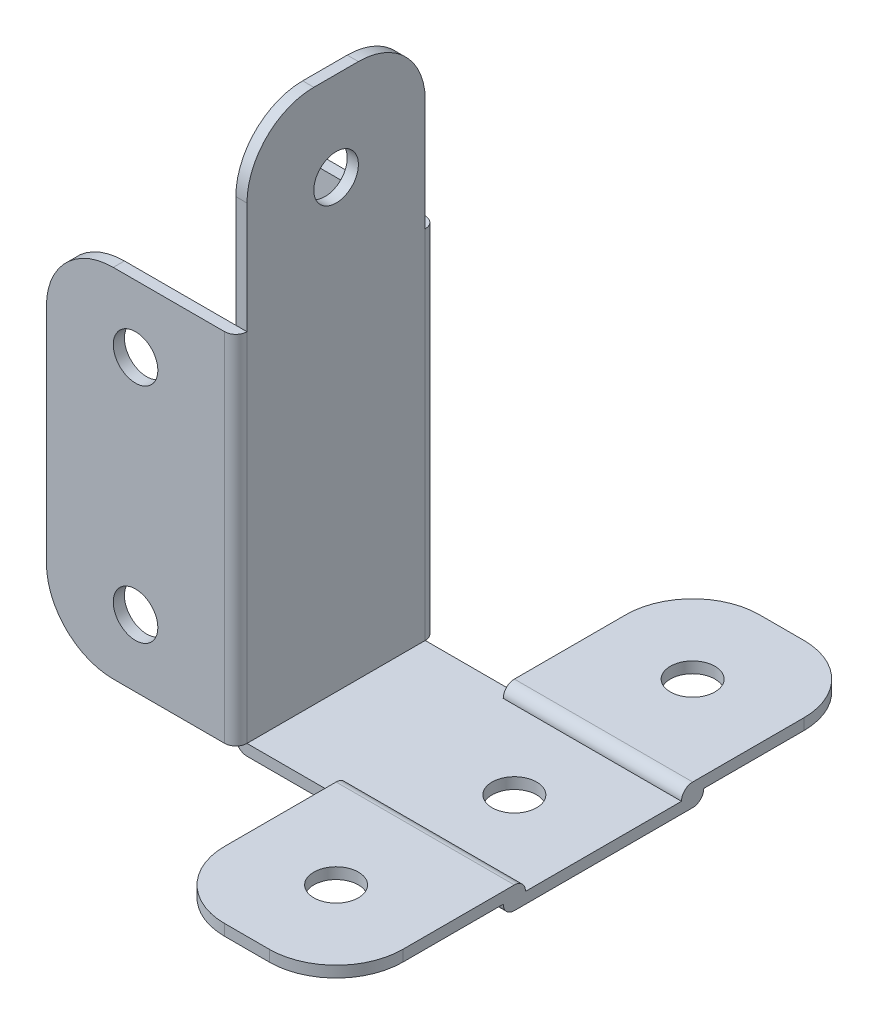
SolidWorks part; units mm, degrees
ref_plane "Front Plane" through (0, 0, 0) normal (0, 0, 1) x (1, 0, 0)
ref_plane "Top Plane" through (0, 0, 0) normal (0, 1, 0) x (1, 0, 0)
ref_plane "Right Plane" through (0, 0, 0) normal (1, 0, 0) x (0, 0, -1)
sketch "Sketch1" plane through (0, 0, 0) normal (0, 0, 1) x (1, 0, 0)
  line L0 (0, 0) -> (-25.4, 0)
  line L1 (-25.4, 0) -> (-25.4, 50.8)
  line L2 (-25.4, 50.8) -> (0, 50.8)
  line L3 (0, 50.8) -> (0, 0)
  line L4 (-12.7, 50.8) -> (-12.7, 0) construction
  circle A0 centre (-12.7, 41.275) radius 3.175
  circle A1 centre (-12.7, 9.525) radius 3.175
  dimension "D5" = 6.35
  dimension "D1" = 9.525
  dimension "D2" = 31.75
  dimension "D3" = 9.525
  dimension "D4" = 25.4
extrude "Boss-Extrude1" add sketch "Sketch1" along normal blind 1.5875
extrude "Boss-Extrude2" add sketch "Sketch1<2>" against normal blind 1.5875 from offset 25.4 separate body offset against normal yes
sketch "Sketch1<2>" plane through (0, 0, 0) normal (0, 0, 1) x (1, 0, 0) same geometry as "Sketch1"
sketch "Sketch3" plane through (0, 0, 0) normal (1, 0, 0) x (0, 0, -1)
  line L0 (25.4, 76.2) -> (0, 50.8) construction
  line L1 (25.4, 50.8) -> (0, 50.8) construction
  line L2 (25.4, 50.8) -> (25.4, 0)
  line L3 (25.4, 0) -> (0, 0)
  line L4 (0, 50.8) -> (0, 0)
  line L5 (25.4, 50.8) -> (0, 50.8) construction
  line L6 (25.4, 50.8) -> (25.4, 76.2)
  line L7 (25.4, 76.2) -> (0, 76.2)
  line L8 (0, 50.8) -> (0, 76.2)
  circle A0 centre (12.7, 63.5) radius 3.175
  dimension "D2" = 6.35
  dimension "D1" = 25.4
extrude "Boss-Extrude3" add sketch "Sketch3" along normal blind 1.5875 separate body
sketch "Sketch4" plane through (0, 0, 0) normal (0, 1, 0) x (1, 0, 0)
  line L1 (14.2875, -50.8) -> (39.6875, -50.8) construction
  line L3 (39.6875, 50.8) -> (14.2875, 50.8)
  line L4 (14.2875, 50.8) -> (14.2875, 25.4)
  line L5 (14.2875, 25.4) -> (14.2875, 0)
  line L6 (14.2875, 25.4) -> (39.6875, 25.4)
  line L7 (39.6875, 50.8) -> (39.6875, 25.4)
  line L8 (14.2875, -25.4) -> (39.6875, -25.4)
  line L9 (26.9875, -50.8) -> (26.9875, 50.8) construction
  line L10 (39.6875, -25.4) -> (39.6875, -50.8) construction
  line L11 (14.2875, 0) -> (14.2875, -25.4)
  line L12 (14.2875, -50.8) -> (14.2875, -25.4) construction
  line L13 (39.6875, -25.4) -> (39.6875, 25.4)
  line L14 (1.5875, 25.4) -> (14.2875, 25.4)
  line L15 (1.5875, 0) -> (14.2875, 0)
  line L16 (1.5875, 25.4) -> (1.5875, 0)
  line L17 (14.2875, 0) -> (39.6875, 0)
  circle A0 centre (26.9875, 12.7) radius 3.175
  circle A1 centre (26.9875, -12.7) radius 3.175
  circle A2 centre (26.9875, -38.1) radius 3.175 construction
  circle A3 centre (26.9875, 38.1) radius 3.175
  dimension "D2" = 6.35
  dimension "D1" = 12.7
  dimension "D3" = 12.7
  dimension "D4" = 25.4
  dimension "D5" = 12.7
  dimension "D6" = 12.7
  dimension "D7" = 12.7
  dimension "D8" = 12.7
  dimension "D9" = 25.4
  dimension "D10" = 12.7
extrude "Boss-Extrude4" add sketch "Sketch4" against normal blind 1.5875 separate body contours L14 L16 L15 L5 | L5 L17 L13 L6 A0 region at (39.3283, 0, -12.7) region at (7.9375, 0, -12.7)
sketch "Sketch6" plane through (0, 0, 0) normal (1, 0, 0) x (0, 0, -1)
  line L4 (0, 0) -> (0, 50.8)
  line L5 (0, 50.8) -> (-1.5875, 50.8)
  line L6 (-1.5875, 50.8) -> (-1.5875, 0)
  line L7 (-1.5875, 0) -> (0, 0)
  line L8 (0, 0) -> (0, 50.8)
  line L9 (0, 50.8) -> (-1.5875, 50.8)
  line L10 (-1.5875, 50.8) -> (-1.5875, 0)
  line L11 (-1.5875, 0) -> (0, 0)
  dimension "D1" = 0
revolve "Revolve1" add sketch "Sketch6" angle 90 about L8
sketch "Sketch7" plane through (0, 0, 0) normal (1, 0, 0) x (0, 0, -1)
  line L4 (25.4, 50.8) -> (25.4, 0)
  line L5 (25.4, 0) -> (26.9875, 0)
  line L6 (26.9875, 0) -> (26.9875, 50.8)
  line L7 (26.9875, 50.8) -> (25.4, 50.8)
  line L8 (25.4, 50.8) -> (25.4, 0)
  line L9 (25.4, 0) -> (26.9875, 0)
  line L10 (26.9875, 0) -> (26.9875, 50.8)
  line L11 (26.9875, 50.8) -> (25.4, 50.8)
  dimension "D1" = 0
revolve "Revolve2" add sketch "Sketch7" angle 90 about L8
sketch "Sketch8" plane through (1.5875, 0, 0) normal (-1, 0, 0) x (0, 0, 1)
  line L4 (0, 0) -> (-25.4, 0)
  line L5 (-25.4, 0) -> (-25.4, -1.5875)
  line L7 (0, -1.5875) -> (0, 0)
  line L9 (-25.4, 0) -> (-25.4, -1.5875)
  line L11 (0, -1.5875) -> (0, 0)
  line L14 (0, 0) -> (-25.4, 0)
  line L16 (-25.4, -1.5875) -> (0, -1.5875)
  line L17 (-25.4, -1.5875) -> (0, -1.5875)
  dimension "D1" = 0
revolve "Revolve3" add sketch "Sketch8" angle 90 about L14
sketch "Sketch9" plane through (0, 0, 0) normal (0, 1, 0) x (1, 0, 0)
  line L0 (14.2875, 25.4) -> (14.2875, 50.8)
  line L1 (14.2875, 50.8) -> (39.6875, 50.8)
  line L2 (39.6875, 50.8) -> (39.6875, 25.4)
  line L3 (39.6875, 25.4) -> (14.2875, 25.4)
  line L4 (14.2875, 0) -> (39.6875, 0)
  line L5 (39.6875, -25.4) -> (39.6875, 25.4) construction
  line L6 (39.6875, 0) -> (39.6875, -25.4)
  line L8 (39.6875, -25.4) -> (14.2875, -25.4)
  line L10 (14.2875, -25.4) -> (14.2875, 0)
  line L11 (26.9875, -50.8) -> (26.9875, 50.8) construction
  circle A0 centre (26.9875, 38.1) radius 3.175 construction
  circle A1 centre (26.9875, -12.7) radius 3.175 construction
  circle A2 centre (26.9875, 38.1) radius 3.175
  circle A3 centre (26.9875, -12.7) radius 3.175
  point P8 (26.9875, 34.925)
  point P11 (26.9875, -9.525)
extrude "Boss-Extrude5" add sketch "Sketch9" along normal blind 1.5875 contours L10 L8 L6 L4 A3 | L3 L2 L1 L0 A2 region at (14.6467, 0, -38.1) region at (26.9875, 0, 0.3592)
sketch "Sketch12" plane through (0, 0, -25.4) normal (0, 0, 1) x (1, 0, 0)
  line L4 (14.2875, 0) -> (39.6875, 0)
  line L5 (39.6875, 0) -> (39.6875, 1.5875)
  line L6 (39.6875, 1.5875) -> (14.2875, 1.5875)
  line L7 (14.2875, 1.5875) -> (14.2875, 0)
  line L8 (14.2875, 0) -> (39.6875, 0)
  line L9 (39.6875, 0) -> (39.6875, 1.5875)
  line L10 (39.6875, 1.5875) -> (14.2875, 1.5875)
  line L11 (14.2875, 1.5875) -> (14.2875, 0)
  dimension "D1" = 0
revolve "Revolve6" add sketch "Sketch12" angle 360 about L8
sketch "Sketch13" plane through (0, 0, 0) normal (0, 0, -1) x (-1, 0, 0)
  line L8 (-39.6875, 0) -> (-14.2875, 0)
  line L9 (-14.2875, 0) -> (-14.2875, 1.5875)
  line L10 (-14.2875, 1.5875) -> (-39.6875, 1.5875)
  line L11 (-39.6875, 1.5875) -> (-39.6875, 0)
  line L12 (-39.6875, 0) -> (-14.2875, 0)
  line L13 (-14.2875, 0) -> (-14.2875, 1.5875)
  line L14 (-14.2875, 1.5875) -> (-39.6875, 1.5875)
  line L15 (-39.6875, 1.5875) -> (-39.6875, 0)
  dimension "D1" = 0
revolve "Revolve7" add sketch "Sketch13" angle 360 about L12
fillet "Fillet6" radius 9.525 10 edges at (14.2875, 0.7937, -50.8) (39.6875, 0.7937, -50.8) (14.2875, 0.7937, 25.4) (39.6875, 0.7937, 25.4) (-25.4, 0, 0.7937) (-25.4, 0, -26.1937) (-25.4, 50.8, 0.7937) (-25.4, 50.8, -26.1937) (0.7937, 76.2, 0) (0.7937, 76.2, -25.4)
